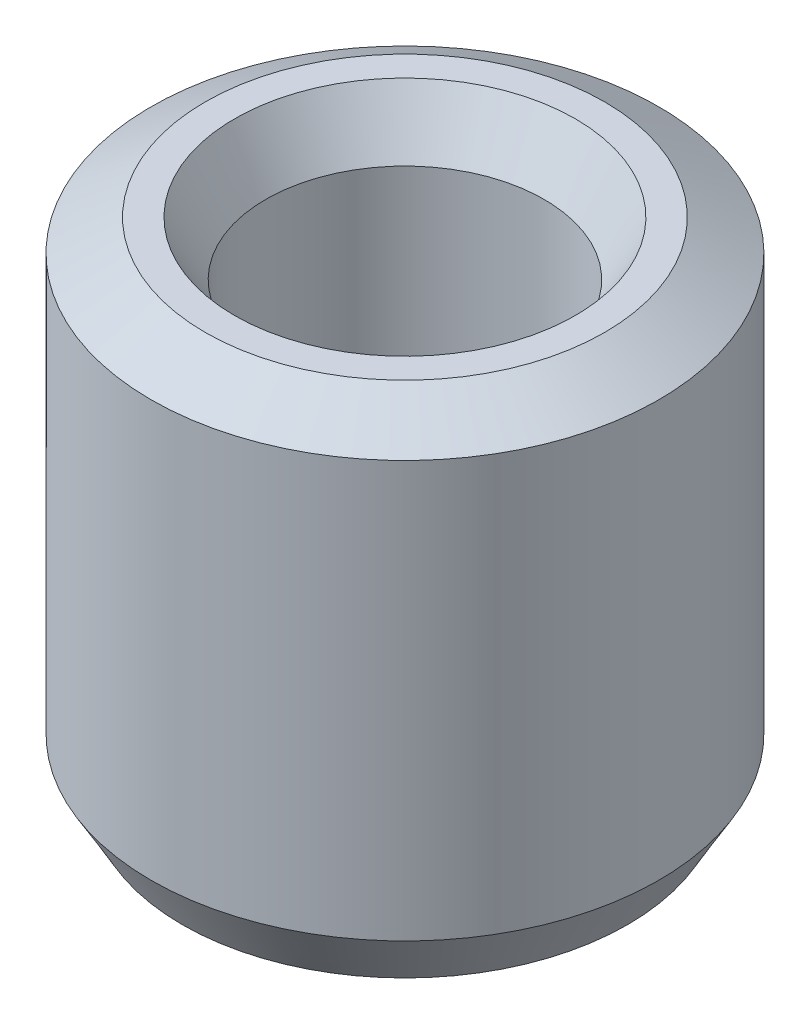
SolidWorks part; units mm, degrees
ref_plane "Front Plane" through (0, 0, 0) normal (0, 0, 1) x (1, 0, 0)
ref_plane "Top Plane" through (0, 0, 0) normal (0, 1, 0) x (1, 0, 0)
ref_plane "Right Plane" through (0, 0, 0) normal (1, 0, 0) x (0, 0, -1)
sketch "Sketch1" plane through (0, 0, 0) normal (0, 1, 0) x (1, 0, 0)
  circle A0 centre (0, 0) radius 12.5
  dimension "SLEEVE_OD" = 25
extrude "Boss-Extrude1" add sketch "Sketch1" along normal blind 24.6971
sketch "Sketch2" plane through (0, 0, 0) normal (0, 1, 0) x (1, 0, 0)
  circle A0 centre (0, 0) radius 6.8529
  dimension "BORE_D" = 13.7058
extrude "Cut-Extrude1" cut sketch "Sketch2" along normal through all
chamfer "Chamfer1" distance 1.5389 angle 60 4 edges at (0, 24.6971, 6.8529) (0, 0, 6.8529) (0, 0, 12.5) (0, 24.6971, 12.5) first distance on face at (0, 24.6971, 6.8529) first distance on face at (0, 0, 6.8529) first distance on face at (0, 24.6971, 12.5)
